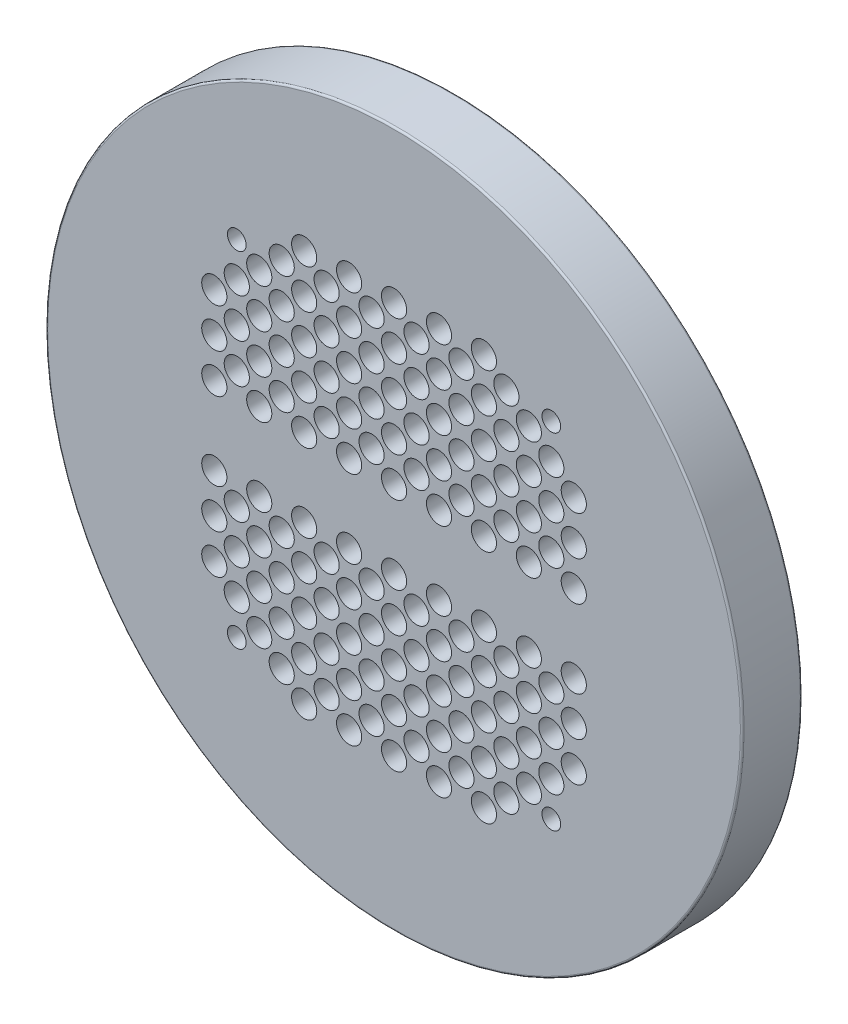
SolidWorks part; units mm, degrees
material "ASTM A105"
ref_plane "Front Plane" through (0, 0, 0) normal (0, 0, 1) x (1, 0, 0)
ref_plane "Top Plane" through (0, 0, 0) normal (0, 1, 0) x (1, 0, 0)
ref_plane "Right Plane" through (0, 0, 0) normal (1, 0, 0) x (0, 0, -1)
ref_axis "Axis1" through (0, 0, -1.27) along (0, 0, 1)
ref_plane "Hub End Plane" through (0, 0, 88.9) normal (0, 0, 1) x (1, 0, 0)
sketch "Sketch1" plane through (0, 0, 0) normal (0, 0, 1) x (1, 0, 0)
  line L0 (0, 314.325) -> (0, 0) construction
  line L1 (41.0276, 311.6359) -> (0, 0) construction
  circle A1 centre (0, 0) radius 295.275
  circle A2 centre (0, 0) radius 314.325 construction
  circle A3 centre (41.0276, 311.6359) radius 17.4625 construction
  dimension "FlangeOD" = 590.55
  dimension "BoltHoleDia" = 34.925
  dimension "BoltCircle" = 628.65
  dimension "HoleOffsetAngle" = 7.5
extrude "Boss-Extrude1" add sketch "Sketch1" along normal blind 50.8
sketch "Sketch7" plane through (0, 0, 0) normal (0, 0, 1) x (1, 0, 0)
  circle A0 centre (0, 0) radius 230.886
  dimension "ID" = 461.772
fillet "Fillet2" radius 1.5875 2 edges at (295.275, 0, 50.8) (295.275, 0, 0)
ref_plane "lug mating plane" through (0, 0, 25.4) normal (0, 0, 1) x (1, 0, 0)
sketch "Sketch11" plane through (0, 0, 0) normal (0, 0, 1) x (1, 0, 0)
  line L0 (-313.3441, 0) -> (312.1404, 0) construction
  line L1 (0, 318.8395) -> (0, -323.6955) construction
  circle A3 centre (0, 33.02) radius 10.668
  circle A15 centre (38.1, 33.02) radius 10.668
  circle A16 centre (76.2, 33.02) radius 10.668
  circle A17 centre (114.3, 33.02) radius 10.668
  circle A18 centre (152.4, 33.02) radius 10.668
  circle A20 centre (-38.1, 33.02) radius 10.668
  circle A21 centre (-76.2, 33.02) radius 10.668
  circle A22 centre (-114.3, 33.02) radius 10.668
  circle A23 centre (-152.4, 33.02) radius 10.668
  circle A88 centre (0, 66.3575) radius 10.668
  circle A89 centre (38.1, 66.3575) radius 10.668
  circle A90 centre (76.2, 66.3575) radius 10.668
  circle A91 centre (114.3, 66.3575) radius 10.668
  circle A93 centre (152.4, 66.3575) radius 10.668
  circle A95 centre (-38.1, 66.3575) radius 10.668
  circle A98 centre (-76.2, 66.3575) radius 10.668
  circle A146 centre (-114.3, 66.3575) radius 10.668
  circle A150 centre (-152.4, 66.3575) radius 10.668
  circle A152 centre (0, 99.695) radius 10.668
  circle A153 centre (38.1, 99.695) radius 10.668
  circle A154 centre (76.2, 99.695) radius 10.668
  circle A156 centre (114.3, 99.695) radius 10.668
  circle A158 centre (152.4, 99.695) radius 10.668
  circle A161 centre (-38.1, 99.695) radius 10.668
  circle A163 centre (-76.2, 99.695) radius 10.668
  circle A164 centre (-114.3, 99.695) radius 10.668
  circle A166 centre (-133.35, 146.05) radius 7.9375
  circle A172 centre (-152.4, 99.695) radius 10.668
  circle A174 centre (0, 133.0325) radius 10.668
  circle A175 centre (38.1, 133.0325) radius 10.668
  circle A176 centre (76.2, 133.0325) radius 10.668
  circle A177 centre (114.3, 133.0325) radius 10.668
  circle A180 centre (-38.1, 133.0325) radius 10.668
  circle A181 centre (-76.2, 133.0325) radius 10.668
  circle A182 centre (-114.3, 133.0325) radius 10.668
  circle A185 centre (0, 166.37) radius 10.668
  circle A186 centre (38.1, 166.37) radius 10.668
  circle A187 centre (76.2, 166.37) radius 10.668
  circle A191 centre (-38.1, 166.37) radius 10.668
  circle A192 centre (-76.2, 166.37) radius 10.668
  circle A207 centre (19.05, 49.8475) radius 10.668
  circle A208 centre (-19.05, 49.8475) radius 10.668
  circle A209 centre (-57.15, 49.8475) radius 10.668
  circle A210 centre (-95.25, 49.8475) radius 10.668
  circle A211 centre (-133.35, 49.8475) radius 10.668
  circle A213 centre (57.15, 49.8475) radius 10.668
  circle A214 centre (95.25, 49.8475) radius 10.668
  circle A215 centre (133.35, 49.8475) radius 10.668
  circle A217 centre (19.05, 83.185) radius 10.668
  circle A218 centre (-19.05, 83.185) radius 10.668
  circle A219 centre (-57.15, 83.185) radius 10.668
  circle A220 centre (-95.25, 83.185) radius 10.668
  circle A221 centre (-133.35, 83.185) radius 10.668
  circle A223 centre (57.15, 83.185) radius 10.668
  circle A224 centre (95.25, 83.185) radius 10.668
  circle A225 centre (133.35, 83.185) radius 10.668
  circle A227 centre (19.05, 116.5225) radius 10.668
  circle A228 centre (-19.05, 116.5225) radius 10.668
  circle A229 centre (-57.15, 116.5225) radius 10.668
  circle A230 centre (-95.25, 116.5225) radius 10.668
  circle A231 centre (-133.35, 116.5225) radius 10.668
  circle A233 centre (57.15, 116.5225) radius 10.668
  circle A234 centre (95.25, 116.5225) radius 10.668
  circle A235 centre (133.35, 116.5225) radius 10.668
  circle A237 centre (19.05, 149.86) radius 10.668
  circle A238 centre (-19.05, 149.86) radius 10.668
  circle A239 centre (-57.15, 149.86) radius 10.668
  circle A240 centre (-95.25, 149.86) radius 10.668
  circle A243 centre (57.15, 149.86) radius 10.668
  circle A244 centre (95.25, 149.86) radius 10.668
  circle A257 centre (-133.35, -146.05) radius 7.9375
  circle A258 centre (133.35, -146.05) radius 7.9375
  circle A262 centre (152.4, 199.7075) radius 10.668 [skipped]
  circle A263 centre (152.4, 166.37) radius 10.668 [skipped]
  circle A265 centre (114.3, 199.7075) radius 10.668 [skipped]
  circle A267 centre (-152.4, 199.7075) radius 10.668 [skipped]
  circle A268 centre (-114.3, 199.7075) radius 10.668 [skipped]
  circle A271 centre (-152.4, 166.37) radius 10.668 [skipped]
  circle A275 centre (152.4, 133.0325) radius 10.668 [skipped]
  circle A278 centre (114.3, 166.37) radius 10.668 [skipped]
  circle A280 centre (76.2, 199.7075) radius 10.668 [skipped]
  circle A281 centre (-114.3, 166.37) radius 10.668 [skipped]
  circle A283 centre (-76.2, 199.7075) radius 10.668 [skipped]
  circle A284 centre (-152.4, 133.0325) radius 10.668 [skipped]
  circle A288 centre (-190.5, 33.02) radius 10.668 [skipped]
  circle A290 centre (190.5, 33.02) radius 10.668 [skipped]
  circle A291 centre (38.1, 199.7075) radius 10.668 [skipped]
  circle A292 centre (0, 199.7075) radius 10.668 [skipped]
  circle A293 centre (-38.1, 199.7075) radius 10.668 [skipped]
  circle A294 centre (133.35, 146.05) radius 7.9375
  circle A303 centre (95.25, -149.86) radius 10.668
  circle A304 centre (57.15, -149.86) radius 10.668
  circle A305 centre (-95.25, -149.86) radius 10.668
  circle A306 centre (-57.15, -149.86) radius 10.668
  circle A307 centre (-19.05, -149.86) radius 10.668
  circle A308 centre (19.05, -149.86) radius 10.668
  circle A309 centre (133.35, -116.5225) radius 10.668
  circle A310 centre (95.25, -116.5225) radius 10.668
  circle A311 centre (57.15, -116.5225) radius 10.668
  circle A312 centre (-133.35, -116.5225) radius 10.668
  circle A313 centre (-95.25, -116.5225) radius 10.668
  circle A314 centre (-57.15, -116.5225) radius 10.668
  circle A315 centre (-19.05, -116.5225) radius 10.668
  circle A316 centre (19.05, -116.5225) radius 10.668
  circle A318 centre (133.35, -83.185) radius 10.668
  circle A319 centre (95.25, -83.185) radius 10.668
  circle A320 centre (57.15, -83.185) radius 10.668
  circle A322 centre (-133.35, -83.185) radius 10.668
  circle A323 centre (-95.25, -83.185) radius 10.668
  circle A324 centre (-57.15, -83.185) radius 10.668
  circle A325 centre (-19.05, -83.185) radius 10.668
  circle A326 centre (19.05, -83.185) radius 10.668
  circle A328 centre (133.35, -49.8475) radius 10.668
  circle A329 centre (95.25, -49.8475) radius 10.668
  circle A330 centre (57.15, -49.8475) radius 10.668
  circle A332 centre (-133.35, -49.8475) radius 10.668
  circle A333 centre (-95.25, -49.8475) radius 10.668
  circle A334 centre (-57.15, -49.8475) radius 10.668
  circle A335 centre (-19.05, -49.8475) radius 10.668
  circle A336 centre (19.05, -49.8475) radius 10.668
  circle A337 centre (-76.2, -166.37) radius 10.668
  circle A338 centre (-38.1, -166.37) radius 10.668
  circle A339 centre (76.2, -166.37) radius 10.668
  circle A340 centre (38.1, -166.37) radius 10.668
  circle A341 centre (0, -166.37) radius 10.668
  circle A342 centre (-114.3, -133.0325) radius 10.668
  circle A343 centre (-76.2, -133.0325) radius 10.668
  circle A344 centre (-38.1, -133.0325) radius 10.668
  circle A345 centre (114.3, -133.0325) radius 10.668
  circle A346 centre (76.2, -133.0325) radius 10.668
  circle A347 centre (38.1, -133.0325) radius 10.668
  circle A348 centre (0, -133.0325) radius 10.668
  circle A349 centre (-152.4, -99.695) radius 10.668
  circle A350 centre (-114.3, -99.695) radius 10.668
  circle A351 centre (-76.2, -99.695) radius 10.668
  circle A352 centre (-38.1, -99.695) radius 10.668
  circle A353 centre (152.4, -99.695) radius 10.668
  circle A354 centre (114.3, -99.695) radius 10.668
  circle A355 centre (76.2, -99.695) radius 10.668
  circle A356 centre (38.1, -99.695) radius 10.668
  circle A357 centre (0, -99.695) radius 10.668
  circle A358 centre (-152.4, -66.3575) radius 10.668
  circle A359 centre (-114.3, -66.3575) radius 10.668
  circle A360 centre (-76.2, -66.3575) radius 10.668
  circle A361 centre (-38.1, -66.3575) radius 10.668
  circle A362 centre (152.4, -66.3575) radius 10.668
  circle A363 centre (114.3, -66.3575) radius 10.668
  circle A364 centre (76.2, -66.3575) radius 10.668
  circle A365 centre (38.1, -66.3575) radius 10.668
  circle A366 centre (0, -66.3575) radius 10.668
  circle A367 centre (-152.4, -33.02) radius 10.668
  circle A368 centre (-114.3, -33.02) radius 10.668
  circle A369 centre (-76.2, -33.02) radius 10.668
  circle A370 centre (-38.1, -33.02) radius 10.668
  circle A371 centre (152.4, -33.02) radius 10.668
  circle A372 centre (114.3, -33.02) radius 10.668
  circle A373 centre (76.2, -33.02) radius 10.668
  circle A374 centre (38.1, -33.02) radius 10.668
  circle A375 centre (0, -33.02) radius 10.668
  dimension "D2" = 133.35
  dimension "D5" = 99.695
  dimension "D12" = 15.875
  dimension "D3" = 33.02
  dimension "D6" = 133.0325
  dimension "D7" = 166.37
  dimension "D14" = 49.8475
  dimension "D15" = 83.185
  dimension "D16" = 116.5225
  dimension "D17" = 149.86
  dimension "D4" = 66.3575
  dimension "D10" = 6
  dimension "D8" = 6
  dimension "D9" = 6
extrude "Cut-Extrude4" cut sketch "Sketch11" against normal through all and the other way through all
equation "\"D1@lug mating plane\"=\"FlangeThk@Boss-Extrude1\"/2"
